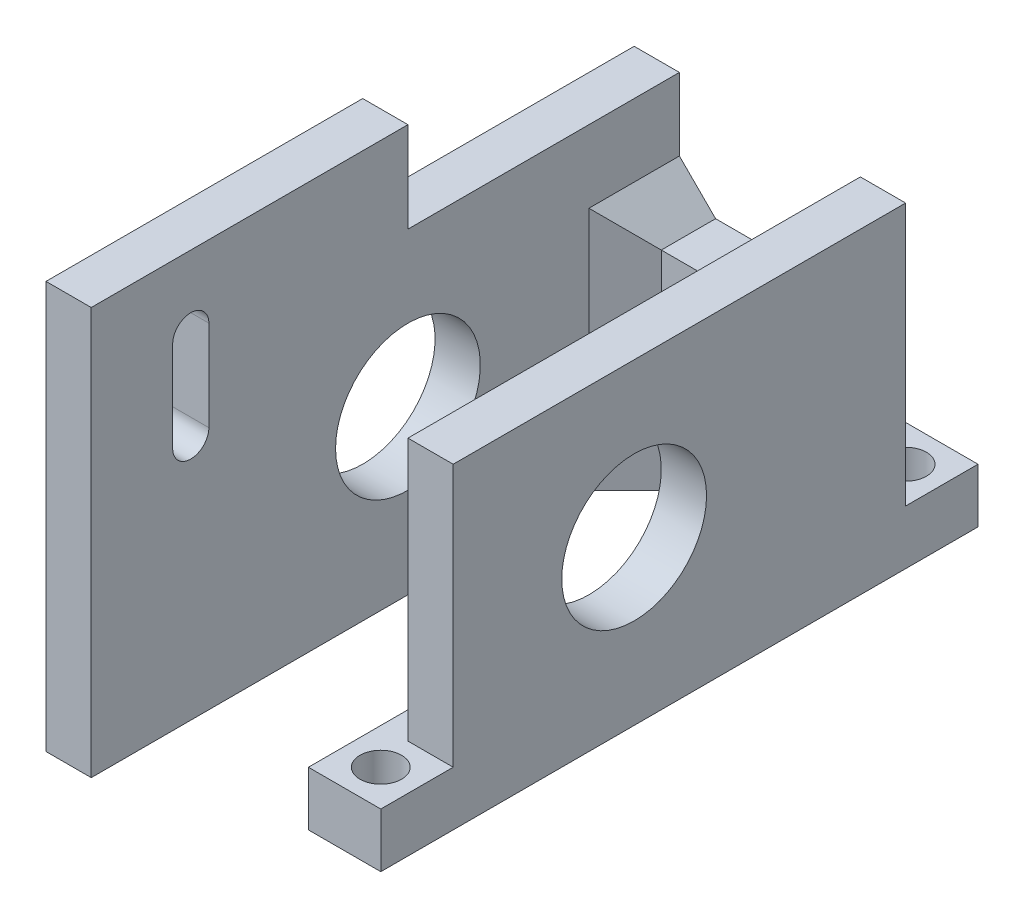
SolidWorks part; units mm, degrees
ref_plane "Plan de face" through (0, 0, 0) normal (0, 0, 1) x (1, 0, 0)
ref_plane "Plan de dessus" through (0, 0, 0) normal (0, 1, 0) x (1, 0, 0)
ref_plane "Plan de droite" through (0, 0, 0) normal (1, 0, 0) x (0, 0, -1)
sketch "Esquisse1" plane through (0, 0, 0) normal (0, 1, 0) x (1, 0, 0)
  line L8 (-23, 9) -> (-23, -41)
  line L9 (-18, 9) -> (-23, 9)
  line L28 (-23, -41) -> (-18, -41)
  line L30 (-18, -41) -> (-18, 3)
  line L31 (7, 3) -> (7, -41)
  line L32 (7, -41) -> (2, -41)
  line L33 (2, -41) -> (2, 3)
  line L35 (-18, 9) -> (2, 9)
  line L38 (-18, 3) -> (2, 3)
  line L39 (-23, -41) -> (-31, -41)
  line L40 (-31, -41) -> (-31, -33)
  line L45 (7, 9) -> (7, 3)
  line L46 (7, 3) -> (-23, 3) construction
  line L47 (-23, 3) -> (-23, 9)
  line L50 (-31, -33) -> (-23, -33)
  line L51 (2, 9) -> (7, 9)
  line L55 (-31, -33) -> (-23, -41) construction
  line L56 (-23, -33) -> (-31, -41) construction
  line L57 (-23, 9) -> (-31, 9)
  line L58 (7, 9) -> (7, 17)
  line L59 (7, 17) -> (-1, 17)
  line L60 (-1, 17) -> (-1, 9)
  line L61 (-1, 9) -> (7, 17) construction
  line L62 (-1, 17) -> (7, 9) construction
  line L63 (7, -41) -> (7, -49)
  line L64 (7, -49) -> (-1, -49)
  line L65 (-1, -49) -> (-1, -37)
  line L66 (-1, -37) -> (2, -37)
  line L67 (7, -49) -> (-1, -41) construction
  line L68 (-1, -41) -> (-1, -49) construction
  line L69 (7, -41) -> (-1, -49) construction
  line L70 (-31, 9) -> (-31, 1)
  line L71 (-31, 1) -> (-23, 1)
  line L72 (-31, 9) -> (-23, 1) construction
  line L73 (-23, 1) -> (-23, 9) construction
  line L74 (-31, 1) -> (-23, 9) construction
  circle A8 centre (3, 13) radius 2.3
  circle A10 centre (3, -45) radius 2.3
  circle A11 centre (-27, -37) radius 2.3
  circle A12 centre (-27, 5) radius 2.3
extrude "Boss.-Extru.1" add sketch "Esquisse1" along normal blind 35 contours L46 | L46 L9 | L46 L35 | L51 L46 region at (-20.5, 0, -8.4169)
extrude "Boss.-Extru.7" add sketch "Esquisse1<6>" along normal blind 8 contours L28 region at (-20.5, 0, -8.4169)
sketch "Esquisse1<6>" plane through (0, 0, 0) normal (0, 1, 0) x (1, 0, 0) same geometry as "Esquisse1"
extrude "Boss.-Extru.8" add sketch "Esquisse1<8>" along normal blind 6 contours L59 L60 L35 L51 L58 A8 | L30 L28 L40 | L66 L65 L64 L63 L32 L33 A10 | L70 L71 L8 L57 A12 | L50 L40 L39 L8 A11 region at (-23.1131, 0, -6) region at (-0.8869, 0, -13) region at (-23.1131, 0, 37) region at (6.8558, 0, 45)
sketch "Esquisse1<8>" plane through (0, 0, 0) normal (0, 1, 0) x (1, 0, 0) same geometry as "Esquisse1"
sketch "Esquisse6" plane through (0, 0, 0) normal (0, -1, 0) x (1, 0, 0)
  line L0 (-18, -3) -> (-14, -3)
  line L1 (-18, -3) -> (2, -3) construction
  line L2 (-18, -3) -> (-18, 1)
  line L3 (-18, 41) -> (-18, -3) construction
  line L4 (-18, 1) -> (-14, -3)
  line L5 (2, -3) -> (-2, -3)
  line L6 (-2, -3) -> (2, 1)
  line L7 (2, 37) -> (2, -3) construction
  line L8 (2, 1) -> (2, -3)
extrude "Boss.-Extru.9" add sketch "Esquisse6" against normal blind 35
sketch "Esquisse8" plane through (-23, 0, 0) normal (-1, 0, 0) x (0, 0, 1)
  line L0 (-9, 0) -> (21, 0) construction
  line L1 (-1, 0) -> (33, 0) construction
  line L2 (21, 0) -> (21, 18) construction
  circle A0 centre (21, 18) radius 8
extrude "Enlèv. mat.-Extru.6" cut sketch "Esquisse8" against normal blind 50 contours A0 region at (-23, 18, 21)
sketch "Esquisse7" plane through (0, 0, -9) normal (0, 0, -1) x (-1, 0, 0)
  line L0 (-7, 35) -> (-2, 35) construction
  line L3 (18, 23) -> (14, 23) construction
  line L8 (-2, 23) -> (2, 23) construction
  line L9 (2, 23) -> (-2, 23) construction
  line L10 (-2, 23) -> (-2, 27) construction
  line L14 (-2, 35) -> (18, 35)
  line L16 (18, 23) -> (18, 27) construction
  line L17 (2, 23) -> (14, 23)
  line L18 (-2, 27) -> (2, 23)
  line L24 (-2, 27) -> (-2, 35)
  line L25 (18, 23) -> (18, 35)
  line L26 (18, 27) -> (14, 23)
  line M8 (23, 35) -> (-7, 35)
extrude "Enlèv. mat.-Extru.5" cut sketch "Esquisse7" against normal blind 35 contours L18 M8 region at (-8, 29.3333, -9)
sketch "Esquisse9" plane through (-23, 0, 0) normal (-1, 0, 0) x (0, 0, 1)
  line L1 (56, 0) -> (56, 45)
  line L6 (21, 18) -> (21, 45) construction
  line L7 (21, 45) -> (21, 35)
  line L8 (21, 45) -> (56, 45)
  line L9 (21, 35) -> (41, 35)
  line L10 (56, 0) -> (41, 0)
  line L11 (41, 0) -> (41, 35)
extrude "Boss.-Extru.10" add sketch "Esquisse9" against normal blind 5
sketch "Esquisse10" plane through (-23, 0, 0) normal (-1, 0, 0) x (0, 0, 1)
  line L0 (45, 45) -> (45, 37) construction
  line L1 (-1, 0) -> (33, 0) construction
  line L2 (21, 0) -> (45, 0) construction
  line L3 (45, 0) -> (45, 45) construction
  line L4 (56, 45) -> (21, 45) construction
  line L5 (45, 45) -> (45, 37) construction
  line L6 (43, 37) -> (43, 27)
  line L7 (43, 27) -> (47, 27) construction
  line L8 (47, 27) -> (47, 37)
  circle A0 centre (45, 37) radius 2
  circle A1 centre (45, 27) radius 2
extrude "Enlèv. mat.-Extru.7" cut sketch "Esquisse10" against normal blind 5 contours A1 | A1 L8 A0 L6 | A0 region at (-23, 32, 45) region at (-23, 27, 45)
